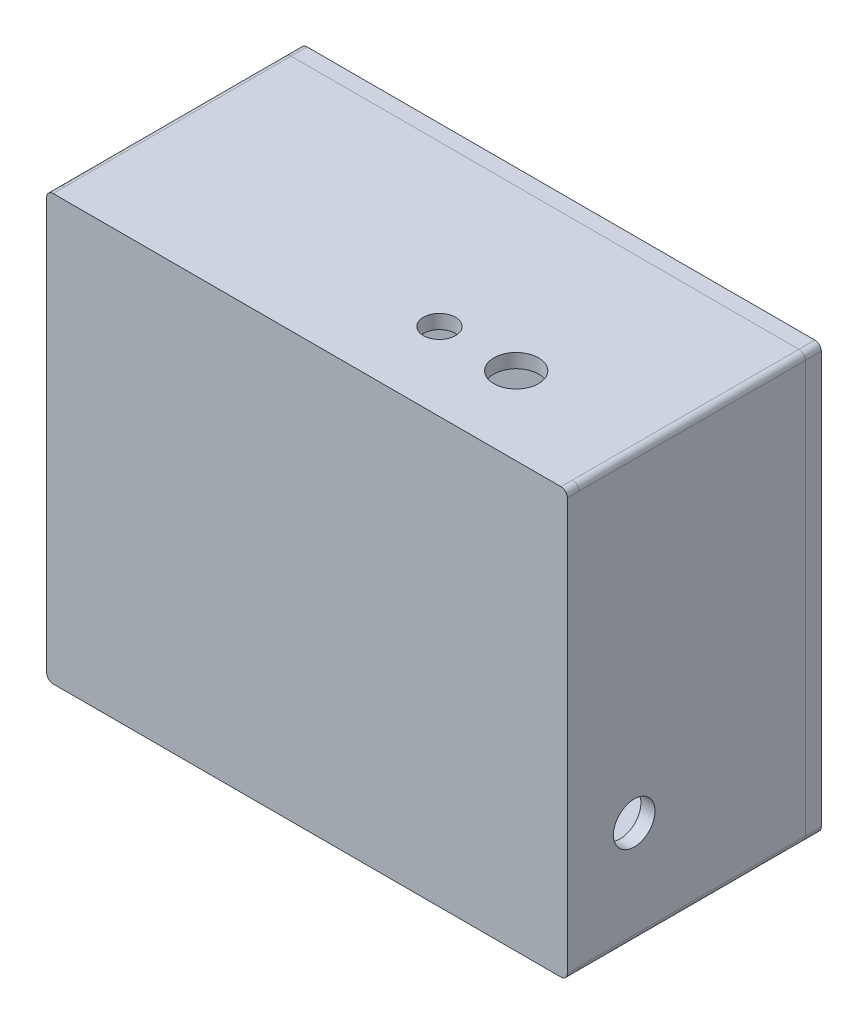
SolidWorks part; units mm, degrees
ref_plane "Alzado" through (0, 0, 0) normal (0, 0, 1) x (1, 0, 0)
ref_plane "Planta" through (0, 0, 0) normal (0, 1, 0) x (1, 0, 0)
ref_plane "Vista lateral" through (0, 0, 0) normal (1, 0, 0) x (0, 0, -1)
sketch "Croquis2" plane through (0, 0, 0) normal (0, 0, 1) x (1, 0, 0)
  line L0 (-40.7, 0) -> (0, 0) construction
  line L1 (40.7, 33.2) -> (-40.7, 33.2)
  line L2 (40.7, 33.2) -> (40.7, -33.2)
  line L3 (40.7, -33.2) -> (-40.7, -33.2)
  line L4 (-40.7, 33.2) -> (-40.7, -33.2)
  line L5 (40.7, 33.2) -> (-40.7, -33.2) construction
  line L6 (40.7, -33.2) -> (-40.7, 33.2) construction
  line L7 (0, 0) -> (40.7, 0) construction
  line L9 (38.5, -31) -> (-38.5, -31) construction
  line L10 (38.5, -31) -> (38.5, 31) construction
  line L11 (38.5, 31) -> (-38.5, 31) construction
  line L12 (-38.5, -31) -> (-38.5, 31) construction
  line L13 (38.5, -31) -> (-38.5, 31) construction
  line L14 (38.5, 31) -> (-38.5, -31) construction
  point P0 (0, 0)
  dimension "D3" = 2.2
  dimension "D4" = 2.2
  dimension "D1" = 77
  dimension "D2" = 62
extrude "Saliente-Extruir1" add sketch "Croquis2" along normal blind 2.5
fillet "Redondeo1" radius 1 4 edges at (-40.7, 33.2, 1.25) (-40.7, -33.2, 1.25) (40.7, -33.2, 1.25) (40.7, 33.2, 1.25)
sketch "Croquis3" plane through (0, 0, 2.5) normal (0, 0, 1) x (1, 0, 0)
  line L4 (38.5, 31) -> (-38.5, 31)
  line L5 (-38.5, 31) -> (-38.5, -31)
  line L6 (-38.5, -31) -> (38.5, -31)
  line L7 (38.5, -31) -> (38.5, 31)
  line L12 (-40.7, 32.2) -> (-40.7, -32.2)
  line L13 (39.7, 33.2) -> (-39.7, 33.2)
  line L14 (40.7, -32.2) -> (40.7, 32.2)
  line L15 (-39.7, -33.2) -> (39.7, -33.2)
  line L16 (-40.7, 32.2) -> (-40.7, -32.2)
  line L17 (39.7, 33.2) -> (-39.7, 33.2)
  line L18 (40.7, -32.2) -> (40.7, 32.2)
  line L19 (-39.7, -33.2) -> (39.7, -33.2)
  arc A0 (-38.5, 31) -> (-38.5, 31) centre (-38.5, 31) ccw
  arc A1 (-38.5, -31) -> (-38.5, -31) centre (-38.5, -31) ccw
  arc A2 (38.5, -31) -> (38.5, -31) centre (38.5, -31) ccw
  arc A3 (38.5, 31) -> (38.5, 31) centre (38.5, 31) ccw
  arc A4 (-39.7, 33.2) -> (-40.7, 32.2) centre (-39.7, 32.2) ccw
  arc A6 (40.7, 32.2) -> (39.7, 33.2) centre (39.7, 32.2) ccw
  arc A8 (39.7, -33.2) -> (40.7, -32.2) centre (39.7, -32.2) ccw
  arc A10 (-40.7, -32.2) -> (-39.7, -33.2) centre (-39.7, -32.2) ccw
  arc A12 (-39.7, 33.2) -> (-40.7, 32.2) centre (-39.7, 32.2) ccw
  arc A13 (40.7, 32.2) -> (39.7, 33.2) centre (39.7, 32.2) ccw
  arc A14 (39.7, -33.2) -> (40.7, -32.2) centre (39.7, -32.2) ccw
  arc A15 (-40.7, -32.2) -> (-39.7, -33.2) centre (-39.7, -32.2) ccw
  dimension "D1" = 0
  dimension "D2" = 2.2
extrude "Saliente-Extruir2" add sketch "Croquis3" along normal blind 35 separate body
sketch "Croquis4" plane through (0, 0, 37.5) normal (0, 0, 1) x (1, 0, 0)
  line L4 (-39.7, -33.2) -> (39.7, -33.2)
  line L5 (40.7, -32.2) -> (40.7, 32.2)
  line L6 (39.7, 33.2) -> (-39.7, 33.2)
  line L7 (-40.7, 32.2) -> (-40.7, -32.2)
  line L12 (-39.7, -33.2) -> (39.7, -33.2)
  line L13 (40.7, -32.2) -> (40.7, 32.2)
  line L14 (39.7, 33.2) -> (-39.7, 33.2)
  line L15 (-40.7, 32.2) -> (-40.7, -32.2)
  arc A4 (-40.7, -32.2) -> (-39.7, -33.2) centre (-39.7, -32.2) ccw
  arc A5 (39.7, -33.2) -> (40.7, -32.2) centre (39.7, -32.2) ccw
  arc A6 (40.7, 32.2) -> (39.7, 33.2) centre (39.7, 32.2) ccw
  arc A7 (-39.7, 33.2) -> (-40.7, 32.2) centre (-39.7, 32.2) ccw
  arc A8 (-40.7, -32.2) -> (-39.7, -33.2) centre (-39.7, -32.2) ccw
  arc A9 (39.7, -33.2) -> (40.7, -32.2) centre (39.7, -32.2) ccw
  arc A10 (40.7, 32.2) -> (39.7, 33.2) centre (39.7, 32.2) ccw
  arc A11 (-39.7, 33.2) -> (-40.7, 32.2) centre (-39.7, 32.2) ccw
  dimension "D1" = 0
extrude "Saliente-Extruir3" add sketch "Croquis4" along normal blind 2.2
sketch "Croquis11" plane through (0, 0, 39.7) normal (0, 0, 1) x (1, 0, 0)
  line L0 (39.7, 33.2) -> (-39.7, 33.2) construction
  line L1 (-39.7, 33.2) -> (-46.7, 33.2)
  line L2 (-39.7, 33.2) -> (-39.7, -33.2)
  line L4 (-46.7, 33.2) -> (-46.7, -33.2)
  line L5 (-39.7, -33.2) -> (39.7, -33.2) construction
  line L6 (0, 0) -> (0, 66.0005) construction
  line L11 (-46.7, -33.2) -> (-39.7, -33.2)
  line L12 (-44.7, 0) -> (-46.7, 0) construction
  line L13 (-44.7, 30.2) -> (-42.7, 30.2)
  line L14 (-44.7, 30.2) -> (-44.7, -30.2)
  line L19 (-44.7, -30.2) -> (-42.7, -30.2)
  line L20 (-42.7, 30.2) -> (-42.7, -30.2)
  line L21 (-42.7, 0) -> (-40.7, 0) construction
  line L24 (-40.7, 32.2) -> (-40.7, -32.2) construction
  line L25 (42.7, 0) -> (40.7, 0) construction
  line L26 (44.7, 0) -> (46.7, 0) construction
  line L27 (42.7, 30.2) -> (42.7, -30.2)
  line L28 (44.7, -30.2) -> (42.7, -30.2)
  line L29 (44.7, 30.2) -> (44.7, -30.2)
  line L30 (44.7, 30.2) -> (42.7, 30.2)
  line L31 (46.7, -33.2) -> (39.7, -33.2)
  line L32 (46.7, 33.2) -> (46.7, -33.2)
  line L33 (39.7, 33.2) -> (39.7, -33.2)
  line L34 (39.7, 33.2) -> (46.7, 33.2)
  dimension "D2" = 3
  dimension "D1" = 7
  dimension "D4" = 60.4
  dimension "D5" = 2
  dimension "D3" = 3
extrude "Saliente-Extruir6" add sketch "Croquis11" against normal blind 1.8
fillet "Redondeo3" radius 2 4 edges at (-46.7, 33.2, 38.8) (-46.7, -33.2, 38.8) (46.7, -33.2, 38.8) (46.7, 33.2, 38.8)
sketch "Croquis7" plane through (0, 0, 37.5) normal (0, 0, -1) x (-1, 0, 0)
  line L0 (0, 0) -> (-42.7, 0) construction
  line L1 (0, 0) -> (0, -33.2) construction
  line L2 (-40.7, -32.2) -> (-40.7, 32.2) construction
  line L3 (39.7, -33.2) -> (-39.7, -33.2) construction
  line L5 (-42.7, 30.2) -> (-42.7, -30.2) construction
  circle A6 centre (-35.5, -28) radius 3.25
  circle A7 centre (-35.5, -28) radius 1.6
  circle A8 centre (-35.5, 28) radius 1.6
  circle A9 centre (-35.5, 28) radius 3.25
  circle A12 centre (35.5, 28) radius 3.25
  circle A13 centre (35.5, 28) radius 1.6
  circle A14 centre (35.5, -28) radius 1.6
  circle A15 centre (35.5, -28) radius 3.25
  dimension "D1" = 6.5
  dimension "D2" = 3.2
  dimension "D3" = 5.2
  dimension "D4" = 5.2
extrude "Saliente-Extruir4" add sketch "Croquis7" against normal blind 8 from offset 28.5
sketch "Croquis14" plane through (0, 0, 2.5) normal (0, 0, 1) x (1, 0, 0)
  line L20 (38, -30.5) -> (38, 30.5)
  line L21 (-38, -30.5) -> (38, -30.5)
  line L22 (-38, 30.5) -> (-38, -30.5)
  line L23 (38, 30.5) -> (-38, 30.5)
  line L24 (38, -30.5) -> (38, 30.5)
  line L25 (-38, -30.5) -> (38, -30.5)
  line L26 (-38, 30.5) -> (-38, -30.5)
  line L27 (38, 30.5) -> (-38, 30.5)
  dimension "D1" = 0.5
extrude "Saliente-Extruir8" add sketch "Croquis14" along normal blind 1.2
sketch "Croquis12" plane through (0, 0, 9) normal (0, 0, -1) x (-1, 0, 0)
  line L0 (-38.5, -28) -> (-37.1, -29.2694)
  line L1 (-38.5, -26.75) -> (-38.5, -29.25) construction
  line L2 (-37.1, -29.2694) -> (-35.5, -31)
  line L3 (-35.5, -31) -> (-38.7665, -31)
  line L4 (-38.7665, -31) -> (-38.7665, -30.1814)
  line L5 (-38.7665, -30.1814) -> (-38.5, -28)
  line L6 (0, 0) -> (0, -10.7992) construction
  line L7 (0, 0) -> (-13.7582, 0) construction
  line L8 (-38.7665, 30.1814) -> (-38.5, 28)
  line L9 (-38.7665, 31) -> (-38.7665, 30.1814)
  line L10 (-35.5, 31) -> (-38.7665, 31)
  line L11 (-36.6839, 29.3483) -> (-35.5, 31)
  line L12 (-38.5, 28) -> (-36.6839, 29.3483)
  line L13 (38.5, 28) -> (36.7228, 30.1814)
  line L14 (36.7228, 30.1814) -> (35.5, 31)
  line L15 (35.5, 31) -> (38.7665, 31)
  line L16 (38.7665, 31) -> (38.7665, 30.1814)
  line L17 (38.7665, 30.1814) -> (38.5, 28)
  line L18 (38.7665, -30.1814) -> (38.5, -28)
  line L19 (38.7665, -31) -> (38.7665, -30.1814)
  line L20 (35.5, -31) -> (38.7665, -31)
  line L21 (36.7228, -29.6) -> (35.5, -31)
  line L22 (38.5, -28) -> (36.7228, -29.6)
  line L23 (-36.75, 31) -> (-34.25, 31) construction
extrude "Saliente-Extruir7" add sketch "Croquis12" against normal up to surface (8 mm away) up to face at (36.25, -28.75, 17)
sketch "Croquis8" plane through (0, 0, 0) normal (0, 0, -1) x (-1, 0, 0)
  circle A9 centre (-35.5, -28) radius 1.6 construction
  circle A10 centre (35.5, -28) radius 1.6 construction
  circle A11 centre (35.5, 28) radius 1.6 construction
  circle A12 centre (-35.5, 28) radius 1.6 construction
  circle A13 centre (-35.5, -28) radius 1.6
  circle A14 centre (35.5, -28) radius 1.6
  circle A15 centre (35.5, 28) radius 1.6
  circle A16 centre (-35.5, 28) radius 1.6
extrude "Cortar-Extruir3" cut sketch "Croquis8" against normal blind 6
sketch "Croquis9" plane through (0, 0, 9) normal (0, 0, -1) x (-1, 0, 0)
  line L0 (-33.8257, -30.9) -> (-31.8514, -30.9)
  line L1 (-33.8257, -30.9) -> (-32.1514, -28) construction
  line L2 (-32.1514, -28) -> (-33.8257, -25.1) construction
  line L3 (-33.8257, -25.1) -> (-37.1743, -25.1)
  line L4 (-37.1743, -25.1) -> (-38.8486, -28)
  line L5 (-38.8486, -28) -> (-37.1743, -30.9)
  line L6 (-37.1743, -30.9) -> (-33.8257, -30.9)
  line L7 (-31.8514, -30.9) -> (-31.8514, -25.1)
  line L8 (-31.8514, -25.1) -> (-33.8257, -25.1)
  line L9 (0, 0) -> (-89.3864, 0) construction
  line L10 (0, 0) -> (0, -53.6215) construction
  line L11 (-32.1514, 28) -> (-33.8257, 25.1) construction
  line L12 (-33.8257, 30.9) -> (-32.1514, 28) construction
  line L13 (-31.8514, 25.1) -> (-33.8257, 25.1)
  line L14 (-31.8514, 30.9) -> (-31.8514, 25.1)
  line L15 (-37.1743, 30.9) -> (-33.8257, 30.9)
  line L16 (-38.8486, 28) -> (-37.1743, 30.9)
  line L17 (-37.1743, 25.1) -> (-38.8486, 28)
  line L18 (-33.8257, 25.1) -> (-37.1743, 25.1)
  line L19 (-33.8257, 30.9) -> (-31.8514, 30.9)
  line L20 (33.8257, 30.9) -> (32.1514, 28) construction
  line L21 (32.1514, 28) -> (33.8257, 25.1) construction
  line L22 (32.1514, -28) -> (33.8257, -25.1) construction
  line L23 (33.8257, -30.9) -> (32.1514, -28) construction
  line L24 (33.8257, 30.9) -> (31.8514, 30.9)
  line L25 (33.8257, 25.1) -> (37.1743, 25.1)
  line L26 (37.1743, 25.1) -> (38.8486, 28)
  line L27 (38.8486, 28) -> (37.1743, 30.9)
  line L28 (37.1743, 30.9) -> (33.8257, 30.9)
  line L29 (31.8514, 30.9) -> (31.8514, 25.1)
  line L30 (31.8514, 25.1) -> (33.8257, 25.1)
  line L31 (31.8514, -25.1) -> (33.8257, -25.1)
  line L32 (31.8514, -30.9) -> (31.8514, -25.1)
  line L33 (37.1743, -30.9) -> (33.8257, -30.9)
  line L34 (38.8486, -28) -> (37.1743, -30.9)
  line L35 (37.1743, -25.1) -> (38.8486, -28)
  line L36 (33.8257, -25.1) -> (37.1743, -25.1)
  line L37 (33.8257, -30.9) -> (31.8514, -30.9)
  circle A0 centre (-35.5, -28) radius 2.9 construction
  circle A1 centre (-35.5, -28) radius 1.6 construction
  circle A3 centre (-35.5, 28) radius 2.9 construction
  circle A4 centre (35.5, 28) radius 2.9 construction
  circle A5 centre (35.5, -28) radius 2.9 construction
  dimension "D1" = 5.8
  dimension "D2" = 0.3
extrude "Cortar-Extruir4" cut sketch "Croquis9" against normal blind 4 from offset 2 offset against normal yes
fillet "Redondeo4" radius 5 8 edges at (-36.375, 31, 17) (-38.5, 28.875, 17) (38.5, -28.875, 17) (36.375, -31, 17) (-38.5, -28.875, 17) (-36.375, -31, 17) (36.375, 31, 17) (38.5, 28.875, 17)
fillet "Redondeo5" radius 1 8 edges at (34.25, -31, 15.5) (38.5, -26.75, 15.5) (-38.5, -26.75, 15.5) (-34.25, -31, 15.5) (-34.25, 31, 15.5) (-38.5, 26.75, 15.5) (34.25, 31, 15.5) (38.5, 26.75, 15.5)
fillet "Redondeo6" radius 1 8 edges at (-44.7, -30.2, 38.8) (-42.7, -30.2, 38.8) (-44.7, 30.2, 38.8) (-42.7, 30.2, 38.8) (44.7, 30.2, 38.8) (42.7, 30.2, 38.8) (44.7, -30.2, 38.8) (42.7, -30.2, 38.8)
sketch "Croquis13" plane through (0, 0, 0) normal (0, 0, -1) x (-1, 0, 0)
  circle A0 centre (-35.5, 28) radius 2.75
  circle A1 centre (35.5, 28) radius 2.75
  circle A2 centre (35.5, -28) radius 2.75
  circle A3 centre (-35.5, -28) radius 2.75
  dimension "D1" = 5.5
extrude "Cortar-Extruir5" cut sketch "Croquis13" against normal blind 2
sketch "Croquis16" plane through (0, 0, 3.7) normal (0, 0, 1) x (1, 0, 0)
  line L0 (-38, -30.5) -> (38, -30.5) construction
  line L1 (2.377, -11.6) -> (25.377, -11.6)
  line L2 (2.377, -11.6) -> (2.377, -12.8)
  line L3 (2.377, -12.8) -> (25.377, -12.8)
  line L4 (25.377, -11.6) -> (25.377, -12.8)
  dimension "D1" = 1.2
  dimension "D2" = 17.7
  dimension "D3" = 23
extrude "Saliente-Extruir9" [suppressed] add sketch "Croquis16" along normal blind 3.5
sketch "Croquis15" plane through (0, -33.2, 0) normal (0, -1, 0) x (1, 0, 0)
  line L0 (-6.7, 4.3) -> (-14.7, 4.3)
  line L9 (-5.7, 19.4) -> (21.3, 19.4) construction
  line L10 (-5.7, 5.3) -> (-5.7, 7.8)
  line L11 (-6.7, 19.4) -> (-14.7, 19.4)
  line L12 (-5.7, 20.4) -> (-5.7, 22.9)
  line L13 (-6.7, 23.9) -> (-14.7, 23.9)
  line L14 (-15.7, 20.4) -> (-15.7, 22.9)
  line L15 (-6.7, 8.8) -> (-14.7, 8.8)
  line L24 (-15.7, 5.3) -> (-15.7, 7.8)
  line L25 (-5.7, 19.4) -> (-15.7, 23.9) construction
  line L30 (-5.7, 23.9) -> (-15.7, 19.4) construction
  line L31 (-5.7, 4.3) -> (-15.7, 8.8) construction
  line L32 (21.3, 19.4) -> (8.3, 19.4)
  line L33 (21.3, 19.4) -> (21.3, 10.3)
  line L34 (21.3, 10.3) -> (8.3, 10.3)
  line L35 (8.3, 19.4) -> (8.3, 10.3)
  line L36 (31.75, 22) -> (38.5, 22)
  line L37 (31.75, 9) -> (31.75, 22)
  line L38 (38.5, 9) -> (31.75, 9)
  line L39 (38.5, 2.5) -> (38.5, 9)
  line L40 (-38.5, 2.5) -> (38.5, 2.5)
  line L41 (-38.5, 9) -> (-38.5, 2.5)
  line L42 (-31.75, 9) -> (-38.5, 9)
  line L43 (-31.75, 22) -> (-31.75, 9)
  line L44 (-38.5, 22) -> (-31.75, 22)
  line L45 (-38.5, 37.5) -> (-38.5, 22)
  line L46 (38.5, 37.5) -> (-38.5, 37.5)
  line L47 (38.5, 22) -> (38.5, 37.5)
  line L48 (31.75, 22) -> (38.5, 22) construction
  line L49 (31.75, 9) -> (31.75, 22) construction
  line L50 (38.5, 9) -> (31.75, 9) construction
  line L51 (38.5, 2.5) -> (38.5, 9) construction
  line L52 (-38.5, 2.5) -> (38.5, 2.5) construction
  line L53 (-38.5, 9) -> (-38.5, 2.5) construction
  line L54 (-31.75, 9) -> (-38.5, 9) construction
  line L55 (-31.75, 22) -> (-31.75, 9) construction
  line L56 (-38.5, 22) -> (-31.75, 22) construction
  line L57 (-38.5, 37.5) -> (-38.5, 22) construction
  line L58 (38.5, 37.5) -> (-38.5, 37.5) construction
  line L59 (38.5, 22) -> (38.5, 37.5) construction
  line L60 (-5.7, 8.8) -> (-15.7, 4.3) construction
  line L61 (-38, 3.7) -> (38, 3.7) construction
  line L62 (-5.7, 20.4) -> (-5.7, 5.3) construction
  arc A0 (-5.7, 22.9) -> (-6.7, 23.9) centre (-6.7, 22.9) ccw
  arc A1 (-6.7, 19.4) -> (-5.7, 20.4) centre (-6.7, 20.4) ccw
  arc A2 (-14.7, 19.4) -> (-15.7, 20.4) centre (-14.7, 20.4) cw
  arc A3 (-14.7, 23.9) -> (-15.7, 22.9) centre (-14.7, 22.9) ccw
  arc A4 (-5.7, 7.8) -> (-6.7, 8.8) centre (-6.7, 7.8) ccw
  arc A5 (-6.7, 4.3) -> (-5.7, 5.3) centre (-6.7, 5.3) ccw
  arc A6 (-14.7, 4.3) -> (-15.7, 5.3) centre (-14.7, 5.3) cw
  arc A7 (-14.7, 8.8) -> (-15.7, 7.8) centre (-14.7, 7.8) ccw
  point P2 (-10.7, 21.65)
  point P33 (-10.7, 6.55)
  dimension "D9" = 1
  dimension "D10" = 1
  dimension "D1" = 0
  dimension "D2" = 10
  dimension "D3" = 4.5
  dimension "D4" = 18.1
  dimension "D5" = 54.2
  dimension "D6" = 13
  dimension "D7" = 9.1
  dimension "D8" = 37
  dimension "D11" = 8
  dimension "D12" = 2.5
  dimension "D13" = 4.5
  dimension "D14" = 5.1
  dimension "D15" = 10.6
extrude "Cortar-Extruir6" cut sketch "Croquis15" against normal blind 10
sketch "Croquis18" plane through (0, 0, 0) normal (0, 0, -1) x (-1, 0, 0)
  line L0 (-39.7, 33.2) -> (39.7, 33.2) construction
  line L1 (-5.75, 23.2) -> (5.75, 23.2)
  line L2 (-5.75, 23.2) -> (-5.75, 20.2)
  line L3 (-5.75, 20.2) -> (5.75, 20.2)
  line L4 (5.75, 23.2) -> (5.75, 20.2)
  line L5 (0, 0) -> (0, 20.2) construction
  dimension "D1" = 11.5
  dimension "D2" = 3
  dimension "D3" = 10
extrude "Cortar-Extruir7" [suppressed] cut sketch "Croquis18" against normal blind 10
sketch "Croquis20" plane through (38.5, 0, 0) normal (-1, 0, 0) x (0, 0, 1)
  line L0 (26, -17.05) -> (32.5, -17.05) construction
  line L1 (29.25, -13.8) -> (29.25, -20.3) construction
  line L12 (9, -31) -> (9, -24.25)
  line L13 (9, -24.25) -> (22, -24.25)
  line L14 (22, -24.25) -> (22, -31)
  line L15 (22, -31) -> (37.5, -31)
  line L16 (37.5, -31) -> (37.5, 31)
  line L17 (37.5, 31) -> (22, 31)
  line L18 (22, 31) -> (22, 24.25)
  line L19 (22, 24.25) -> (9, 24.25)
  line L20 (9, 24.25) -> (9, 31)
  line L21 (9, 31) -> (2.5, 31)
  line L22 (2.5, 31) -> (2.5, -31)
  line L23 (2.5, -31) -> (9, -31)
  line L24 (9, -31) -> (9, -24.25) construction
  line L25 (9, -24.25) -> (22, -24.25) construction
  line L26 (22, -24.25) -> (22, -31) construction
  line L27 (22, -31) -> (37.5, -31) construction
  line L28 (37.5, -31) -> (37.5, 31) construction
  line L29 (37.5, 31) -> (22, 31) construction
  line L30 (22, 31) -> (22, 24.25) construction
  line L31 (22, 24.25) -> (9, 24.25) construction
  line L32 (9, 24.25) -> (9, 31) construction
  line L33 (9, 31) -> (2.5, 31) construction
  line L34 (2.5, 31) -> (2.5, -31) construction
  line L35 (2.5, -31) -> (9, -31) construction
  circle A0 centre (29.25, -17.05) radius 3.25
  dimension "D2" = 6.5
  dimension "D3" = 11.5
  dimension "D4" = 17.2
  dimension "D1" = 0
extrude "Cortar-Extruir8" cut sketch "Croquis20" against normal blind 10
sketch "Croquis21" plane through (0, 33.2, 0) normal (0, 1, 0) x (1, 0, 0)
  line L0 (38.5, -37.5) -> (-38.5, -37.5) construction
  line L1 (38.5, -37.5) -> (38.5, -22) construction
  circle A0 centre (8.5, -27.5) radius 2.5
  circle A1 centre (20.5, -27.5) radius 3.5
  dimension "D1" = 7
  dimension "D2" = 5
  dimension "D3" = 10
  dimension "D4" = 12
  dimension "D5" = 18
extrude "Cortar-Extruir9" cut sketch "Croquis21" against normal blind 10
sketch "Croquis19" plane through (0, 0, 37.5) normal (0, 0, -1) x (-1, 0, 0)
  line L0 (38.5, -31) -> (-38.5, -31) construction
  line L1 (32.5, -31) -> (-38.5, -31) construction
  line L2 (32.5, -31) -> (32.5, 24) construction
  line L3 (32.5, 24) -> (-38.5, 24) construction
  line L4 (-38.5, -31) -> (-38.5, 24) construction
  line L5 (32.5, -31) -> (-38.5, 24) construction
  line L6 (32.5, 24) -> (-38.5, -31) construction
  line L7 (-38.5, -31) -> (-38.5, 31) construction
  line L8 (-38.5, 31) -> (38.5, 31) construction
  line L9 (-27.5, 25) -> (-23.5, 25)
  line L10 (-27.5, 25) -> (-27.5, 31)
  line L11 (-27.5, 31) -> (-23.5, 31)
  line L12 (-23.5, 25) -> (-23.5, 31)
  line L13 (0, 0) -> (0, 38.2457) construction
  line L14 (23.5, 25) -> (23.5, 31)
  line L15 (27.5, 31) -> (23.5, 31)
  line L16 (27.5, 25) -> (27.5, 31)
  line L17 (27.5, 25) -> (23.5, 25)
  line L18 (-38.5, -31) -> (-38.5, 31) construction
  line L19 (38.5, 31) -> (38.5, -31) construction
  line L20 (38.5, 20) -> (33.5, 20)
  line L21 (38.5, 20) -> (38.5, 16)
  line L22 (38.5, 16) -> (33.5, 16)
  line L23 (33.5, 20) -> (33.5, 16)
  line L24 (38.5, 31) -> (31.75, 31) construction
  line L25 (0, 0) -> (13.0372, 0) construction
  line L26 (33.5, -20) -> (33.5, -16)
  line L27 (38.5, -16) -> (33.5, -16)
  line L28 (38.5, -20) -> (38.5, -16)
  line L29 (38.5, -20) -> (33.5, -20)
  line L30 (32.5, 31) -> (32.5, -24) construction
  point P0 (0, 0)
  dimension "D1" = 71
  dimension "D2" = 55
  dimension "D3" = 1
  dimension "D4" = 4
  dimension "D5" = 6
  dimension "D6" = 11
  dimension "D7" = 1
  dimension "D8" = 4
  dimension "D9" = 11
extrude "Saliente-Extruir10" add sketch "Croquis19" along normal blind 2
sketch "Croquis22" plane through (0, 0, 35.5) normal (0, 0, -1) x (-1, 0, 0)
  line L0 (-27.5, 25) -> (-27.5, 31) construction
  line L1 (-27.5, 31) -> (-23.5, 31)
  line L2 (-27.5, 31) -> (-27.5, 23.8)
  line L3 (-26.5, 22.8) -> (-24.5, 22.8)
  line L4 (-23.5, 31) -> (-23.5, 23.8)
  line L5 (32.5, 24) -> (-38.5, 24) construction
  line L6 (0, 38.2457) -> (0, 0) construction
  line L7 (23.5, 31) -> (23.5, 23.8)
  line L8 (26.5, 22.8) -> (24.5, 22.8)
  line L9 (27.5, 31) -> (27.5, 23.8)
  line L10 (27.5, 31) -> (23.5, 31)
  line L11 (32.5, -31) -> (32.5, 24) construction
  line L12 (38.5, 20) -> (32.3, 20)
  line L13 (38.5, 20) -> (38.5, 16)
  line L14 (38.5, 16) -> (32.3, 16)
  line L15 (31.3, 19) -> (31.3, 17)
  line L16 (0, 0) -> (13.0372, 0) construction
  line L17 (31.3, -19) -> (31.3, -17)
  line L18 (38.5, -16) -> (32.3, -16)
  line L19 (38.5, -20) -> (38.5, -16)
  line L20 (38.5, -20) -> (32.3, -20)
  arc A0 (-27.5, 23.8) -> (-26.5, 22.8) centre (-26.5, 23.8) ccw
  arc A1 (-24.5, 22.8) -> (-23.5, 23.8) centre (-24.5, 23.8) ccw
  arc A2 (24.5, 22.8) -> (23.5, 23.8) centre (24.5, 23.8) cw
  arc A3 (27.5, 23.8) -> (26.5, 22.8) centre (26.5, 23.8) cw
  arc A4 (32.3, 16) -> (31.3, 17) centre (32.3, 17) cw
  arc A5 (32.3, 20) -> (31.3, 19) centre (32.3, 19) ccw
  arc A6 (32.3, -20) -> (31.3, -19) centre (32.3, -19) cw
  arc A7 (32.3, -16) -> (31.3, -17) centre (32.3, -17) ccw
  dimension "D2" = 1
  dimension "D4" = 1
  dimension "D1" = 1.2
  dimension "D3" = 1.2
extrude "Saliente-Extruir11" add sketch "Croquis22" along normal blind 1.3
fillet "Redondeo7" radius 1 20 edges at (-35.4, -16, 34.2) (-31.5929, -16.2929, 34.2) (-35.4, -20, 34.2) (-31.5929, -19.7071, 34.2) (27.5, 27.4, 34.2) (27.2071, 23.0929, 34.2) (23.5, 27.4, 34.2) (23.7929, 23.0929, 34.2) (-23.5, 27.4, 34.2) (-23.7929, 23.0929, 34.2) (-27.5, 27.4, 34.2) (-27.2071, 23.0929, 34.2) (-35.4, 20, 34.2) (-31.5929, 19.7071, 34.2) (-35.4, 16, 34.2) (-31.5929, 16.2929, 34.2) (-31.3, -18, 34.2) (25.5, 22.8, 34.2) (-25.5, 22.8, 34.2) (-31.3, 18, 34.2)
sketch "Croquis23" plane through (0, 0, 0) normal (0, 0, -1) x (-1, 0, 0)
  line L0 (-40.7, -32.2) -> (-40.7, 32.2) construction
  line L1 (-46.8584, 34.6862) -> (-40.7, 34.6862)
  line L2 (-46.8584, 34.6862) -> (-46.8584, -36.9503)
  line L3 (-46.8584, -36.9503) -> (-40.7, -36.9503)
  line L4 (-40.7, 34.6862) -> (-40.7, -36.9503)
  line L5 (40.7, 32.2) -> (40.7, -32.2) construction
  line L6 (40.7, 37.1677) -> (55.3063, 37.1677)
  line L7 (40.7, 37.1677) -> (40.7, -42.1234)
  line L8 (40.7, -42.1234) -> (55.3063, -42.1234)
  line L9 (55.3063, 37.1677) -> (55.3063, -42.1234)
extrude "Cortar-Extruir10" cut sketch "Croquis23" against normal through all
sketch "Croquis24" plane through (0, 0, 0) normal (0, 0, -1) x (-1, 0, 0)
  line L0 (0, 0) -> (0, 52.6867) construction
  line L1 (0, 0) -> (-48.4324, 0) construction
  circle A0 centre (-35.5, 28) radius 2.5
  circle A1 centre (35.5, 28) radius 2.5
  circle A2 centre (35.5, -28) radius 2.5
  circle A3 centre (-35.5, -28) radius 2.5
  dimension "D1" = 5
extrude "Saliente-Extruir12" add sketch "Croquis24" along normal blind 0.6 and the other way blind 1 separate body
sketch "Croquis25" plane through (0, 0, -0.6) normal (0, 0, -1) x (-1, 0, 0)
  line L0 (-35.5, 28) -> (-35.5, 29.6) construction
  line L1 (-35.5, 28) -> (-37.1, 28) construction
  line L2 (-35.5, 28) -> (-35.5, 26.4) construction
  line L3 (-35.5, 28) -> (-33.9, 28) construction
  line L4 (-35.8, 28.3) -> (-35.8, 29.6)
  line L5 (-35.8, 27.7) -> (-37.1, 27.7)
  line L6 (-35.2, 28.3) -> (-33.9, 28.3)
  line L7 (-35.2, 27.7) -> (-35.2, 26.4)
  line L8 (-35.2, 28.3) -> (-35.2, 29.6)
  line L9 (-35.8, 28.3) -> (-37.1, 28.3)
  line L10 (-35.2, 27.7) -> (-33.9, 27.7)
  line L11 (-35.8, 27.7) -> (-35.8, 26.4)
  line L12 (-35.8, 28) -> (-35.8, 29.6) construction
  line L13 (-35.5, 28.3) -> (-37.1, 28.3) construction
  line L14 (-35.5, 28.3) -> (-33.9, 28.3) construction
  line L15 (-35.2, 28) -> (-35.2, 29.6) construction
  line L16 (-35.2, 28) -> (-35.2, 26.4) construction
  line L17 (-35.5, 27.7) -> (-33.9, 27.7) construction
  line L18 (-35.5, 27.7) -> (-37.1, 27.7) construction
  line L19 (-35.8, 28) -> (-35.8, 26.4) construction
  line L20 (0, 0) -> (0, 51.1166) construction
  line L21 (0, 0) -> (-53.1334, 0) construction
  line L22 (35.5, 28) -> (33.9, 28) construction
  line L23 (35.5, 28) -> (35.5, 26.4) construction
  line L24 (35.5, 28) -> (37.1, 28) construction
  line L25 (35.5, 28) -> (35.5, 29.6) construction
  line L26 (35.8, 27.7) -> (35.8, 26.4)
  line L27 (35.2, 27.7) -> (33.9, 27.7)
  line L28 (35.8, 28.3) -> (37.1, 28.3)
  line L29 (35.2, 28.3) -> (35.2, 29.6)
  line L30 (35.2, 27.7) -> (35.2, 26.4)
  line L31 (35.2, 28.3) -> (33.9, 28.3)
  line L32 (35.8, 27.7) -> (37.1, 27.7)
  line L33 (35.8, 28.3) -> (35.8, 29.6)
  line L34 (35.5, -28) -> (35.5, -29.6) construction
  line L35 (35.5, -28) -> (37.1, -28) construction
  line L36 (35.5, -28) -> (35.5, -26.4) construction
  line L37 (35.5, -28) -> (33.9, -28) construction
  line L38 (-35.5, -28) -> (-33.9, -28) construction
  line L39 (-35.5, -28) -> (-35.5, -26.4) construction
  line L40 (-35.5, -28) -> (-37.1, -28) construction
  line L41 (-35.5, -28) -> (-35.5, -29.6) construction
  line L42 (35.8, -28.3) -> (35.8, -29.6)
  line L43 (35.8, -27.7) -> (37.1, -27.7)
  line L44 (35.2, -28.3) -> (33.9, -28.3)
  line L45 (35.2, -27.7) -> (35.2, -26.4)
  line L46 (35.2, -28.3) -> (35.2, -29.6)
  line L47 (35.8, -28.3) -> (37.1, -28.3)
  line L48 (35.2, -27.7) -> (33.9, -27.7)
  line L49 (35.8, -27.7) -> (35.8, -26.4)
  line L50 (-35.8, -27.7) -> (-35.8, -26.4)
  line L51 (-35.2, -27.7) -> (-33.9, -27.7)
  line L52 (-35.8, -28.3) -> (-37.1, -28.3)
  line L53 (-35.2, -28.3) -> (-35.2, -29.6)
  line L54 (-35.2, -27.7) -> (-35.2, -26.4)
  line L55 (-35.2, -28.3) -> (-33.9, -28.3)
  line L56 (-35.8, -27.7) -> (-37.1, -27.7)
  line L57 (-35.8, -28.3) -> (-35.8, -29.6)
  arc A2 (-35.8, 29.6) -> (-35.2, 29.6) centre (-35.5, 29.6) cw
  arc A4 (-37.1, 27.7) -> (-37.1, 28.3) centre (-37.1, 28) cw
  arc A6 (-33.9, 28.3) -> (-33.9, 27.7) centre (-33.9, 28) cw
  arc A8 (-35.2, 26.4) -> (-35.8, 26.4) centre (-35.5, 26.4) cw
  arc A9 (35.2, 26.4) -> (35.8, 26.4) centre (35.5, 26.4) ccw
  arc A10 (33.9, 28.3) -> (33.9, 27.7) centre (33.9, 28) ccw
  arc A11 (37.1, 27.7) -> (37.1, 28.3) centre (37.1, 28) ccw
  arc A12 (35.8, 29.6) -> (35.2, 29.6) centre (35.5, 29.6) ccw
  arc A13 (35.8, -29.6) -> (35.2, -29.6) centre (35.5, -29.6) cw
  arc A14 (37.1, -27.7) -> (37.1, -28.3) centre (37.1, -28) cw
  arc A15 (33.9, -28.3) -> (33.9, -27.7) centre (33.9, -28) cw
  arc A16 (35.2, -26.4) -> (35.8, -26.4) centre (35.5, -26.4) cw
  arc A17 (-35.2, -26.4) -> (-35.8, -26.4) centre (-35.5, -26.4) ccw
  arc A18 (-33.9, -28.3) -> (-33.9, -27.7) centre (-33.9, -28) ccw
  arc A19 (-37.1, -27.7) -> (-37.1, -28.3) centre (-37.1, -28) ccw
  arc A20 (-35.8, -29.6) -> (-35.2, -29.6) centre (-35.5, -29.6) ccw
  dimension "D1" = 1.6
  dimension "D2" = 0.3
  dimension "D3" = 0.3
extrude "Cortar-Extruir11" cut sketch "Croquis25" against normal blind 0.4
sketch "Croquis26" plane through (0, 0, 1) normal (0, 0, 1) x (1, 0, 0)
  line L0 (17.4484, 0) -> (0, 0) construction
  line L1 (0, 0) -> (0, 14.7753) construction
  circle A0 centre (35.5, 28) radius 1.5
  circle A1 centre (35.5, 28) radius 2.5 construction
  circle A2 centre (-35.5, 28) radius 1.5
  circle A3 centre (-35.5, -28) radius 1.5
  circle A4 centre (35.5, -28) radius 1.5
  dimension "D1" = 3
extrude "Saliente-Extruir13" add sketch "Croquis26" along normal blind 16
sketch "Croquis27" plane through (0, 0, 15) normal (0, 0, -1) x (-1, 0, 0)
  line L0 (0, 0) -> (0, 44.0175) construction
  line L1 (-37.0877, 30.75) -> (-38.6754, 28)
  line L2 (-38.6754, 28) -> (-37.0877, 25.25)
  line L3 (-37.0877, 25.25) -> (-33.9123, 25.25)
  line L4 (-36.9671, 25.1) -> (-34.0329, 25.1)
  line L5 (-32.1859, 30.9) -> (-37.1743, 30.9)
  line L6 (-37.1743, 30.9) -> (-38.8486, 28)
  line L7 (-38.8486, 28) -> (-37.2413, 25.2159)
  line L8 (-36.9671, 25.1) -> (-34.0329, 25.1) construction
  line L9 (-32.1859, 30.9) -> (-37.1743, 30.9) construction
  line L10 (-37.1743, 30.9) -> (-38.8486, 28) construction
  line L11 (-38.8486, 28) -> (-37.2413, 25.2159) construction
  line L12 (-33.9123, 25.25) -> (-32.3246, 28)
  line L13 (-32.3246, 28) -> (-33.9123, 30.75)
  line L14 (-33.9123, 30.75) -> (-37.0877, 30.75)
  line L15 (0, 0) -> (-17.4741, 0) construction
  line L16 (38.8486, 28) -> (37.2413, 25.2159) construction
  line L17 (37.1743, 30.9) -> (38.8486, 28) construction
  line L18 (32.1859, 30.9) -> (37.1743, 30.9) construction
  line L19 (36.9671, 25.1) -> (34.0329, 25.1) construction
  line L20 (33.9123, 30.75) -> (37.0877, 30.75)
  line L21 (32.3246, 28) -> (33.9123, 30.75)
  line L22 (33.9123, 25.25) -> (32.3246, 28)
  line L23 (37.0877, 25.25) -> (33.9123, 25.25)
  line L24 (38.6754, 28) -> (37.0877, 25.25)
  line L25 (37.0877, 30.75) -> (38.6754, 28)
  line L26 (36.9671, -25.1) -> (34.0329, -25.1) construction
  line L27 (32.1859, -30.9) -> (37.1743, -30.9) construction
  line L28 (37.1743, -30.9) -> (38.8486, -28) construction
  line L29 (38.8486, -28) -> (37.2413, -25.2159) construction
  line L30 (-38.8486, -28) -> (-37.2413, -25.2159) construction
  line L31 (-37.1743, -30.9) -> (-38.8486, -28) construction
  line L32 (-32.1859, -30.9) -> (-37.1743, -30.9) construction
  line L33 (-36.9671, -25.1) -> (-34.0329, -25.1) construction
  line L34 (37.0877, -30.75) -> (38.6754, -28)
  line L35 (38.6754, -28) -> (37.0877, -25.25)
  line L36 (37.0877, -25.25) -> (33.9123, -25.25)
  line L37 (33.9123, -25.25) -> (32.3246, -28)
  line L38 (32.3246, -28) -> (33.9123, -30.75)
  line L39 (33.9123, -30.75) -> (37.0877, -30.75)
  line L40 (-33.9123, -30.75) -> (-37.0877, -30.75)
  line L41 (-32.3246, -28) -> (-33.9123, -30.75)
  line L42 (-33.9123, -25.25) -> (-32.3246, -28)
  line L43 (-37.0877, -25.25) -> (-33.9123, -25.25)
  line L44 (-38.6754, -28) -> (-37.0877, -25.25)
  line L45 (-37.0877, -30.75) -> (-38.6754, -28)
  circle A0 centre (-35.5, 28) radius 2.75 construction
  circle A1 centre (-35.5, 28) radius 1.7
  arc A2 (37.0294, 25.1324) -> (36.9671, 25.1) centre (35.5, 28) cw construction
  arc A3 (37.0294, 25.1324) -> (37.2413, 25.2159) centre (37.5, 24.25) cw construction
  arc A4 (-34.0329, 25.1) -> (-32.6324, 29.5294) centre (-35.5, 28) ccw
  arc A5 (-32.1859, 30.9) -> (-32.6324, 29.5294) centre (-31.75, 30) ccw
  arc A6 (-37.0294, 25.1324) -> (-37.2413, 25.2159) centre (-37.5, 24.25) ccw
  arc A7 (-37.0294, 25.1324) -> (-36.9671, 25.1) centre (-35.5, 28) ccw
  arc A8 (-34.0329, 25.1) -> (-32.6324, 29.5294) centre (-35.5, 28) ccw construction
  arc A9 (-32.1859, 30.9) -> (-32.6324, 29.5294) centre (-31.75, 30) ccw construction
  arc A10 (-37.0294, 25.1324) -> (-37.2413, 25.2159) centre (-37.5, 24.25) ccw construction
  arc A11 (-37.0294, 25.1324) -> (-36.9671, 25.1) centre (-35.5, 28) ccw construction
  arc A12 (32.1859, 30.9) -> (32.6324, 29.5294) centre (31.75, 30) cw construction
  arc A13 (34.0329, 25.1) -> (32.6324, 29.5294) centre (35.5, 28) cw construction
  circle A14 centre (35.5, 28) radius 2.75 construction
  circle A15 centre (35.5, 28) radius 1.7
  circle A16 centre (35.5, -28) radius 2.75 construction
  arc A17 (34.0329, -25.1) -> (32.6324, -29.5294) centre (35.5, -28) ccw construction
  arc A18 (32.1859, -30.9) -> (32.6324, -29.5294) centre (31.75, -30) ccw construction
  arc A19 (-37.0294, -25.1324) -> (-36.9671, -25.1) centre (-35.5, -28) cw construction
  arc A20 (-37.0294, -25.1324) -> (-37.2413, -25.2159) centre (-37.5, -24.25) cw construction
  arc A21 (-32.1859, -30.9) -> (-32.6324, -29.5294) centre (-31.75, -30) cw construction
  arc A22 (-34.0329, -25.1) -> (-32.6324, -29.5294) centre (-35.5, -28) cw construction
  arc A23 (37.0294, -25.1324) -> (37.2413, -25.2159) centre (37.5, -24.25) ccw construction
  arc A24 (37.0294, -25.1324) -> (36.9671, -25.1) centre (35.5, -28) ccw construction
  circle A25 centre (-35.5, -28) radius 2.75 construction
  circle A26 centre (35.5, -28) radius 1.7
  circle A27 centre (-35.5, -28) radius 1.7
  dimension "D3" = 3.4
  dimension "D2" = 5.5
  dimension "D1" = 0
extrude "Saliente-Extruir14" add sketch "Croquis27" along normal blind 3 separate body
fillet "Redondeo8" radius 1 4 edges at (-40.7, 33.2, 38.8) (40.7, 33.2, 38.8) (40.7, -33.2, 38.8) (-40.7, -33.2, 38.8)
fillet "Redondeo9" radius 1 12 edges at (-38.0087, -30.5087, 19.8386) (38.0087, -30.5087, 19.8386) (38.0087, 30.5087, 19.8386) (-38.0087, 30.5087, 19.8386) (-38.5, -31, 5.75) (-38.5, -31, 29.75) (38.5, -31, 5.75) (38.5, -31, 29.75) (38.5, 31, 5.75) (38.5, 31, 29.75) (-38.5, 31, 29.75) (-38.5, 31, 5.75)
sketch "Croquis28" plane through (0, 0, 0) normal (0, 0, -1) x (-1, 0, 0)
  line L0 (37.5, -31) -> (-37.5, -31) construction
  line L1 (22.7, -12.8) -> (16.6195, -12.8)
  line L2 (22.7, -12.8) -> (22.7, -11.2) construction
  line L3 (22.7, -11.2) -> (16.6195, -11.2)
  line L4 (-1.3, -12.8) -> (-1.3, -11.2) construction
  line L5 (22.7, -12.8) -> (24.3, -12.8) construction
  line L6 (22.7, -12.8) -> (22.7, -24.8)
  line L7 (22.7, -24.8) -> (24.3, -24.8)
  line L8 (24.3, -12.8) -> (24.3, -24.8)
  line L9 (-1.3, -12.8) -> (-2.9, -12.8) construction
  line L10 (-1.3, -12.8) -> (-1.3, -24.8)
  line L11 (-1.3, -24.8) -> (-2.9, -24.8)
  line L12 (-2.9, -12.8) -> (-2.9, -24.8)
  line L13 (10.7, -31) -> (10.7, -12.8) construction
  line L14 (-2.9, -12.8) -> (-1.3, -11.2)
  line L15 (22.7, -11.2) -> (24.3, -12.8)
  line L16 (4.7805, -11.2) -> (-1.3, -11.2)
  line L17 (14.7, -31) -> (6.7, -31)
  line L18 (6.7, -31) -> (6.7, -33.2)
  line L19 (6.7, -33.2) -> (14.7, -33.2)
  line L20 (14.7, -33.2) -> (14.7, -31)
  line L21 (14.7, -31) -> (6.7, -31) construction
  line L22 (6.7, -31) -> (6.7, -33.2) construction
  line L23 (6.7, -33.2) -> (14.7, -33.2) construction
  line L24 (14.7, -33.2) -> (14.7, -31) construction
  line L26 (4.7805, -11.2) -> (4.7805, -12.8)
  line L28 (16.6195, -11.2) -> (16.6195, -12.8)
  line L29 (4.7805, -12.8) -> (-1.3, -12.8)
  line L30 (4.7805, -12.8) -> (10.7, -12.8) construction
  line L31 (10.7, -12.8) -> (16.6195, -12.8) construction
  dimension "D1" = 1.6
  dimension "D2" = 1.6
  dimension "D3" = 1.6
  dimension "D4" = 18.2
  dimension "D5" = 24
  dimension "D7" = 12
  dimension "D8" = 5.9195
  dimension "D6" = 0
extrude "Saliente-Extruir15" add sketch "Croquis28" against normal blind 7 contours L4 L1 L2 L3 | L9 L12 L11 L10 | L6 L7 L8 L15 L3 L14 L12 L11 L10 L1 region at (-19.6598, -12.6438, 0) region at (1.4562, -18.8, 0)
